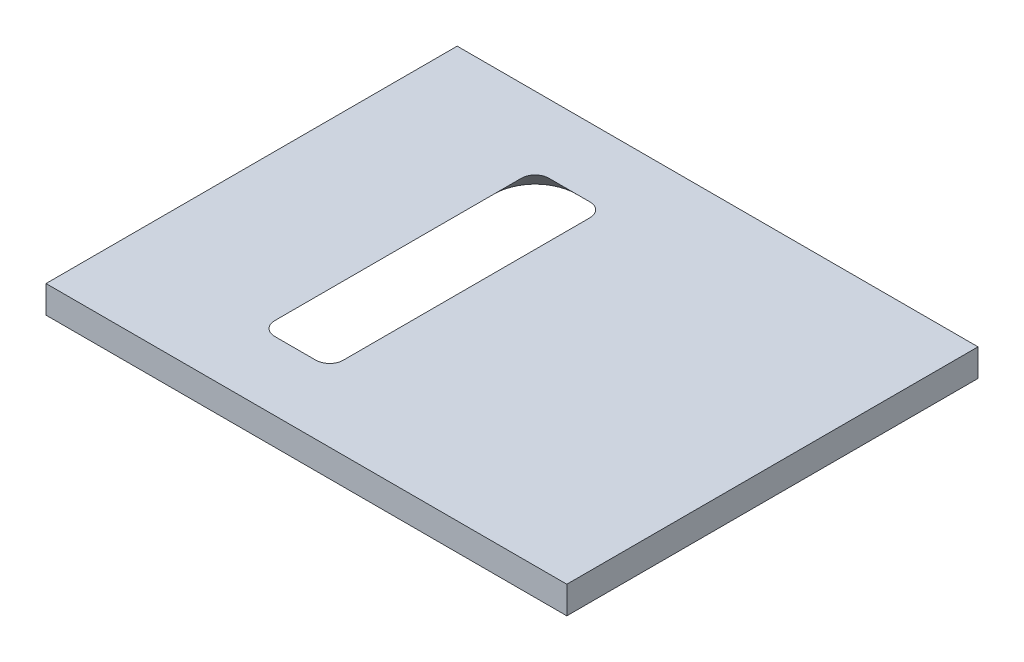
SolidWorks part; units mm, degrees
material "6061-T4 (SS)"
ref_plane "Front Plane" through (0, 0, 0) normal (0, 0, 1) x (1, 0, 0)
ref_plane "Top Plane" through (0, 0, 0) normal (0, 1, 0) x (1, 0, 0)
ref_plane "Right Plane" through (0, 0, 0) normal (1, 0, 0) x (0, 0, -1)
sketch "Sketch2" plane through (0, 0, 0) normal (0, 1, 0) x (1, 0, 0)
  line L5 (-13.189, 15) -> (24.811, 15)
  line L6 (-13.189, 15) -> (-13.189, -15)
  line L7 (-13.189, -15) -> (24.811, -15)
  line L8 (24.811, 15) -> (24.811, -15)
  line L9 (-13.189, 15) -> (24.811, -15) construction
  line L10 (-13.189, -15) -> (24.811, 15) construction
  dimension "D1" = 38
  dimension "D2" = 30
extrude "Boss-Extrude1" add sketch "Sketch2" along normal blind 2
sketch "Sketch4" plane through (0, 2, 0) normal (0, 1, 0) x (1, 0, 0)
  line L1 (1.5, -10) -> (-1.5, -10)
  line L2 (2.5, -9) -> (2.5, 9)
  line L3 (1.5, 10) -> (-1.5, 10)
  line L4 (-2.5, -9) -> (-2.5, 9)
  line L5 (2.5, -10) -> (-2.5, 10) construction
  line L6 (2.5, 10) -> (-2.5, -10) construction
  arc A0 (1.5, -10) -> (2.5, -9) centre (1.5, -9) ccw
  arc A1 (2.5, 9) -> (1.5, 10) centre (1.5, 9) ccw
  arc A2 (-1.5, 10) -> (-2.5, 9) centre (-1.5, 9) ccw
  arc A3 (-1.5, -10) -> (-2.5, -9) centre (-1.5, -9) cw
  point P0 (0, 0)
  dimension "D3" = 1
  dimension "D1" = 20
  dimension "D2" = 5
extrude "Cut-Extrude4" cut sketch "Sketch4" against normal through all draft 45 draft outward yes
sketch "Sketch5" plane through (0, 2, 0) normal (0, 1, 0) x (1, 0, 0)
  line L0 (18.2427, -15) -> (18.2427, 15) construction
  line L1 (-13.189, -15) -> (24.811, -15) construction
  line L2 (24.811, 15) -> (-13.189, 15) construction
  circle A0 centre (18.2427, -10) radius 1.595
  circle A1 centre (18.2427, 10) radius 1.595
  dimension "D3" = 3.19
  dimension "D4" = 3.19
  dimension "D1" = 5
  dimension "D2" = 5
extrude "Cut-Extrude5" [suppressed] cut sketch "Sketch5" against normal through all
